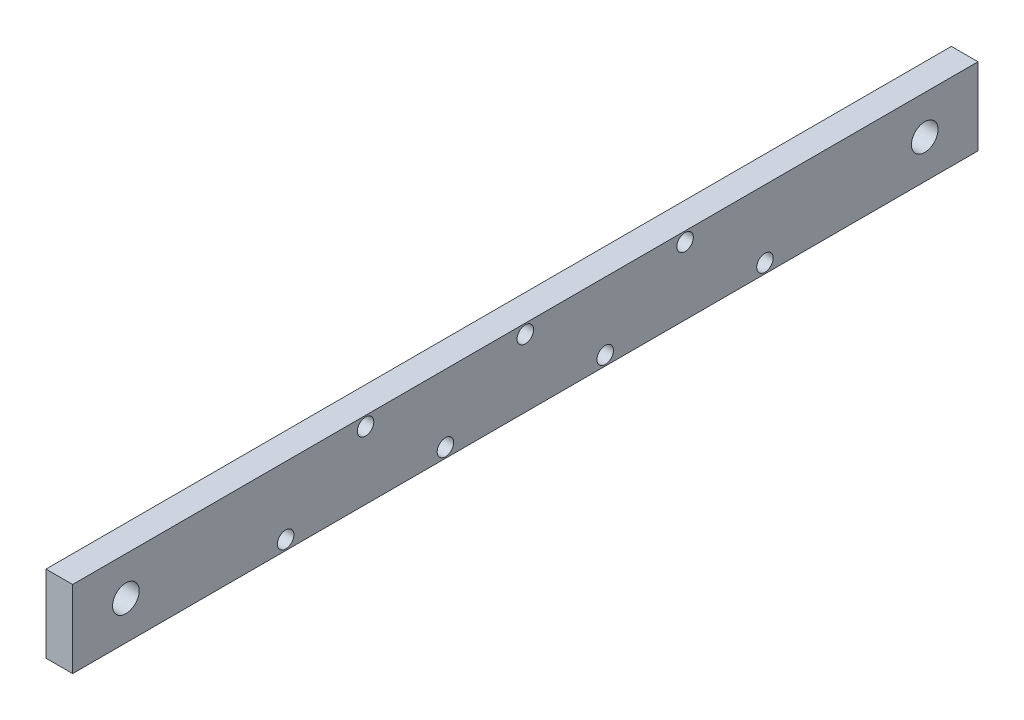
SolidWorks part; units mm, degrees
ref_plane "前视基准面" through (0, 0, 0) normal (0, 0, 1) x (1, 0, 0)
ref_plane "上视基准面" through (0, 0, 0) normal (0, 1, 0) x (1, 0, 0)
ref_plane "右视基准面" through (0, 0, 0) normal (1, 0, 0) x (0, 0, -1)
other "Configuration Table"
sketch "草图1" plane through (0, 0, 0) normal (1, 0, 0) x (0, 0, -1)
  line L0 (-150, 0) -> (150, 0) construction
  line L1 (-170, 14.5) -> (170, 14.5)
  line L2 (-170, 14.5) -> (-170, -14.5)
  line L3 (-170, -14.5) -> (170, -14.5)
  line L4 (170, 14.5) -> (170, -14.5)
  line L8 (-120, 10.8586) -> (120, 10.8586)
  line L9 (-120, 10.8586) -> (-120, -10.8586)
  line L10 (-120, -10.8586) -> (120, -10.8586)
  line L11 (120, 10.8586) -> (120, -10.8586)
  line L12 (-120, 10.8586) -> (120, -10.8586) construction
  line L13 (-120, -10.8586) -> (120, 10.8586) construction
  circle A0 centre (-150, 0) radius 5
  circle A1 centre (150, 0) radius 5
  circle A2 centre (-90, -10.8586) radius 3.1
  circle A3 centre (-30, -10.8586) radius 3.1
  circle A4 centre (30, -10.8586) radius 3.1
  circle A5 centre (-60, 10.8586) radius 3.1
  circle A6 centre (90, -10.8586) radius 3.1
  circle A7 centre (0, 10.8586) radius 3.1
  circle A8 centre (60, 10.8586) radius 3.1
  point P10 (0, 0)
  point P12 (-170, 0)
  point P29 (-100.2427, -10.8586)
  point P30 (-71.2579, -10.8586)
  point P31 (15.2133, -10.8586)
  point P32 (69.9622, -10.8586)
  point P33 (-83.979, 10.8586)
  point P34 (22.1374, 10.8586)
  point P35 (84.9943, 10.8586)
  dimension "D2" = 10
  dimension "D4" = 20
  dimension "D8" = 6.2
  dimension "D1" = 300
  dimension "D3" = 20
  dimension "D5" = 14.5
  dimension "D6" = 120
  dimension "D7" = 10.8586
  dimension "D9" = 30
  dimension "D10" = 60
  dimension "D11" = 60
  dimension "D12" = 60
  dimension "D13" = 60
  dimension "D14" = 60
  dimension "D15" = 60
  dimension "D16" = 60
  dimension "D17" = 30
extrude "凸台-拉伸1" add sketch "草图1" along normal blind 10 contours L1 L4 L3 L2
extrude "切除-拉伸1" cut sketch "草图1<3>" along normal through all contours A2 | A3 | A4 | A6 | A8 | A7 | A5
sketch "草图1<3>" plane through (0, 0, 0) normal (1, 0, 0) x (0, 0, -1) same geometry as "草图1"
extrude "切除-拉伸2" cut sketch "草图1<4>" along normal through all contours A0 | A1
sketch "草图1<4>" plane through (0, 0, 0) normal (1, 0, 0) x (0, 0, -1) same geometry as "草图1"
